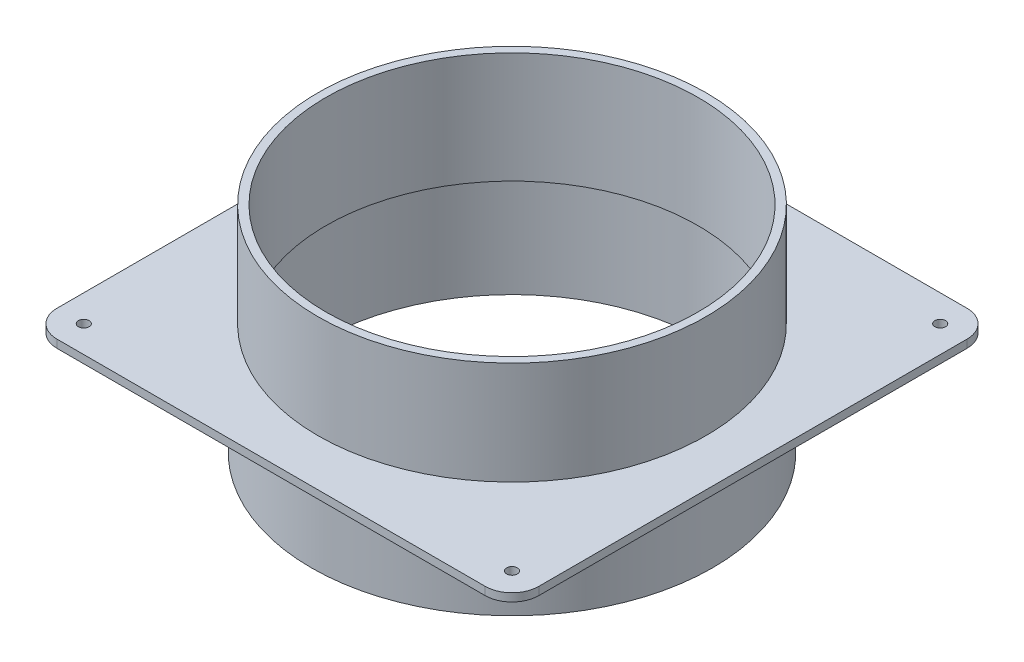
SolidWorks part; units mm, degrees
material "PVC Rigid"
ref_plane "Front Plane" through (0, 0, 0) normal (0, 0, 1) x (1, 0, 0)
ref_plane "Top Plane" through (0, 0, 0) normal (0, 1, 0) x (1, 0, 0)
ref_plane "Right Plane" through (0, 0, 0) normal (1, 0, 0) x (0, 0, -1)
sketch "Sketch1" plane through (0, 0, 0) normal (0, 1, 0) x (1, 0, 0)
  line L0 (-80, 80) -> (-80, -80) construction
  line L1 (80, 90) -> (-80, 90)
  line L2 (90, 80) -> (90, -80)
  line L3 (80, -90) -> (-80, -90)
  line L4 (-90, 80) -> (-90, -80)
  line L5 (90, 90) -> (-90, -90) construction
  line L6 (90, -90) -> (-90, 90) construction
  line L7 (80, -80) -> (-80, -80) construction
  line L8 (80, 80) -> (80, -80) construction
  line L9 (80, 80) -> (-80, 80) construction
  arc A0 (90, -80) -> (80, -90) centre (80, -80) cw
  arc A1 (-80, -90) -> (-90, -80) centre (-80, -80) cw
  arc A2 (-80, 90) -> (-90, 80) centre (-80, 80) ccw
  arc A3 (80, 90) -> (90, 80) centre (80, 80) cw
  arc A5 (-80, -80) -> (-80, -80) centre (-80, -80) cw
  arc A6 (80, -80) -> (80, -80) centre (80, -80) cw
  arc A7 (80, 80) -> (80, 80) centre (80, 80) cw
  arc A8 (-80, 80) -> (-80, 80) centre (-80, 80) ccw
  circle A9 centre (-80, -80) radius 2
  circle A10 centre (80, -80) radius 2
  circle A11 centre (80, 80) radius 2
  circle A12 centre (-80, 80) radius 2
  circle A13 centre (0, 0) radius 69.5
  point P0 (0, 0)
  point P18 (0, 0)
  point P38 (69.3321, 21.1969)
  dimension "D3" = 10
  dimension "D4" = 10
  dimension "D5" = 4
  dimension "D1" = 180
  dimension "D2" = 180
extrude "Boss-Extrude3" add sketch "Sketch1" along normal blind 1.5 and the other way blind 1.5 contours A3 L1 A2 L4 A1 L3 A0 L2 A12 A11 A10 A9 region at (85.2711, 0, -85.2711)
sketch "Sketch2" plane through (0, 0, 0) normal (0, 1, 0) x (1, 0, 0)
  circle A2 centre (0, 0) radius 72.5
  circle A3 centre (0, 0) radius 69.5
  dimension "D2" = 145
  dimension "D1" = 3
extrude "Boss-Extrude4" add sketch "Sketch2" along normal blind 40
sketch "Sketch4" plane through (0, 0, 0) normal (0, 1, 0) x (1, 0, 0)
  circle A2 centre (0, 0) radius 75
  circle A3 centre (0, 0) radius 72
  dimension "D2" = 3
  dimension "D1" = 150
extrude "Boss-Extrude6" add sketch "Sketch4" against normal blind 40
ref_axis "Axis1" through (0, -1.5, 0) along (0, 1, 0)
